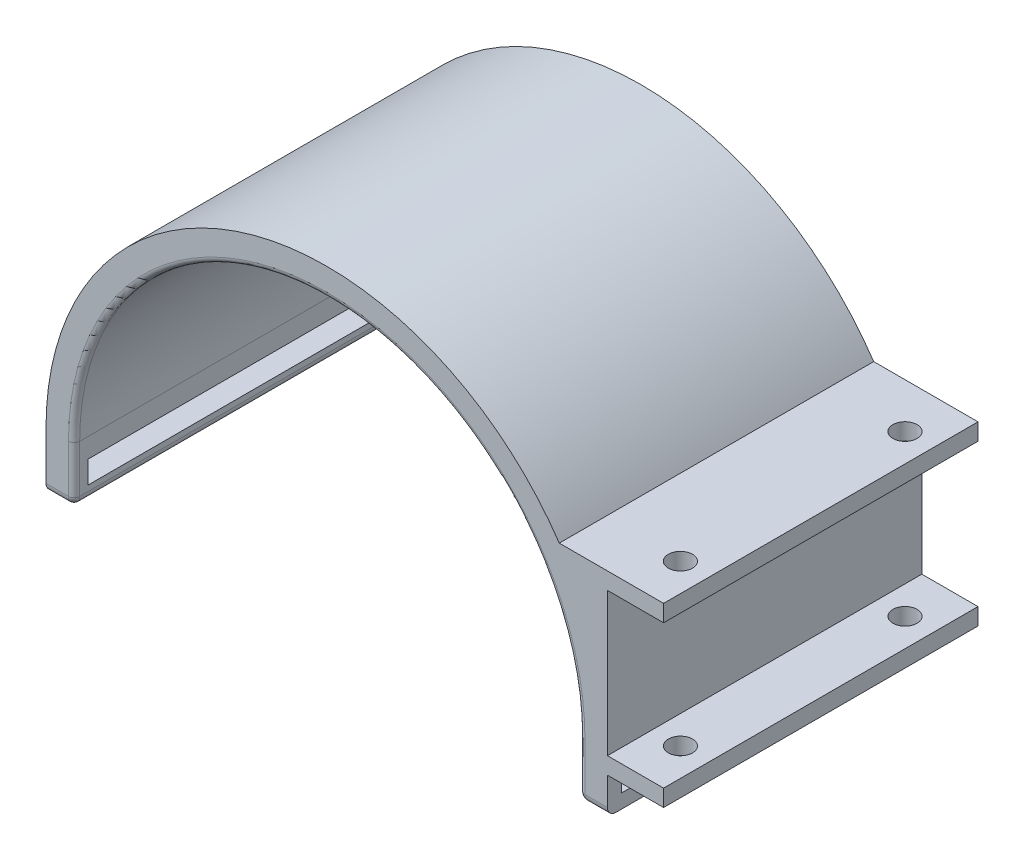
SolidWorks part; units mm, degrees
ref_plane "Front Plane" through (0, 0, 0) normal (0, 0, 1) x (1, 0, 0)
ref_plane "Top Plane" through (0, 0, 0) normal (0, 1, 0) x (1, 0, 0)
ref_plane "Right Plane" through (0, 0, 0) normal (1, 0, 0) x (0, 0, -1)
sketch "Sketch1" plane through (0, 0, 0) normal (0, 0, 1) x (1, 0, 0)
  line L0 (0, 0) -> (90, 0) construction
  line L1 (45, 45) -> (45, 0) construction
  line L2 (0, 0) -> (-5, 0)
  line L3 (90, 0) -> (95, 0)
  line L4 (45, 50) -> (45, 45) construction
  line L5 (95, -10) -> (90, -10)
  line L6 (-5, 0) -> (0, 0)
  line L7 (-5, 0) -> (-5, -10)
  line L8 (-5, -10) -> (0, -10)
  line L9 (0, 0) -> (0, -10)
  line L10 (90, 0) -> (90, -10)
  line L11 (95, 0) -> (90, 0)
  line L12 (95, 0) -> (95, -10)
  arc A0 (0, 0) -> (90, 0) centre (45, 0) cw
  arc A1 (-5, 0) -> (95, 0) centre (45, 0) cw
  dimension "D1" = 90
  dimension "D2" = 45
  dimension "D3" = 5
  dimension "D4" = 5
  dimension "D5" = 10
extrude "Boss-Extrude1" add sketch "Sketch1" along normal blind 56 contours A1 L2 A0 L3 | L12 L3 L10 L5 | L9 L2 L7 L8 region at (-2.5, -5, 0) region at (-2.5, 1.118, 0) region at (92.5, -5, 0)
sketch "Sketch3" plane through (95, 0, 0) normal (1, 0, 0) x (0, 0, -1)
  line L0 (0, 0) -> (0, -10) construction
  line L1 (-53.5, -3.5) -> (-2.5, -3.5)
  line L2 (-53.5, -3.5) -> (-53.5, -7.5)
  line L3 (-53.5, -7.5) -> (-2.5, -7.5)
  line L4 (-2.5, -3.5) -> (-2.5, -7.5)
  line L5 (-56, 0) -> (-56, -10) construction
  line L6 (-56, -10) -> (0, -10) construction
  dimension "D1" = 2.5
  dimension "D2" = 2.5
  dimension "D3" = 2.5
  dimension "D4" = 4
extrude "Cut-Extrude1" cut sketch "Sketch3" against normal through all
sketch "Sketch4" plane through (95, 0, 0) normal (1, 0, 0) x (0, 0, -1)
  line L0 (-2.5, -3.5) -> (0, -3.5) construction
  line L1 (0, 0) -> (0, -10) construction
  line L2 (-56, 50) -> (-56, 0) construction
  line L3 (0, -3.5) -> (-56, -3.5)
  line L4 (0, -3.5) -> (0, 28)
  line L5 (0, 28) -> (-56, 28)
  line L6 (-56, -3.5) -> (-56, 28)
  dimension "D1" = 31.5
extrude "Boss-Extrude3" add sketch "Sketch4" against normal up to next
sketch "Sketch5" plane through (95, 0, 0) normal (1, 0, 0) x (0, 0, -1)
  line L0 (-2.5, -3.5) -> (0, -3.5) construction
  line L1 (0, 28) -> (0, -10) construction
  line L2 (-56, 28) -> (-56, -10) construction
  line L3 (0, -3.5) -> (-56, -3.5)
  line L4 (0, -3.5) -> (0, -0.5)
  line L5 (0, -0.5) -> (-56, -0.5)
  line L6 (-56, -3.5) -> (-56, -0.5)
  line L8 (0, 28) -> (-56, 28)
  line L9 (0, 28) -> (0, 25)
  line L10 (0, 25) -> (-56, 25)
  line L11 (-56, 28) -> (-56, 25)
  dimension "D1" = 3
  dimension "D2" = 3
extrude "Boss-Extrude4" add sketch "Sketch5" along normal blind 10
sketch "Sketch7" plane through (0, 28, 0) normal (0, 1, 0) x (1, 0, 0)
  line L0 (100, 0) -> (100, -56) construction
  line L3 (86.4246, 0) -> (105, 0) construction
  line L4 (86.4246, -56) -> (105, -56) construction
  line L5 (105, 0) -> (105, -56) construction
  line L6 (105, -28) -> (86.4246, -28) construction
  line L7 (86.4246, -56) -> (86.4246, 0) construction
  circle A0 centre (100, -48) radius 2.15
  circle A1 centre (100, -8) radius 2.15
  dimension "D2" = 4.3
  dimension "D3" = 8
  dimension "D1" = 5
extrude "Cut-Extrude3" cut sketch "Sketch7" against normal through all
fillet "Fillet1" radius 1 6 edges at (0, -5, 56) (90, -5, 56) (0, -5, 0) (90, -5, 0) (45, 45, 56) (45, 45, 0)
fillet "Fillet2" radius 1.5 10 edges at (93, -10, 56) (90.2929, -10, 55.7071) (93, -10, 0) (90.2929, -10, 0.2929) (-3, -10, 56) (-0.2929, -10, 55.7071) (-3, -10, 0) (-0.2929, -10, 0.2929) (90, -10, 28) (0, -10, 28)
